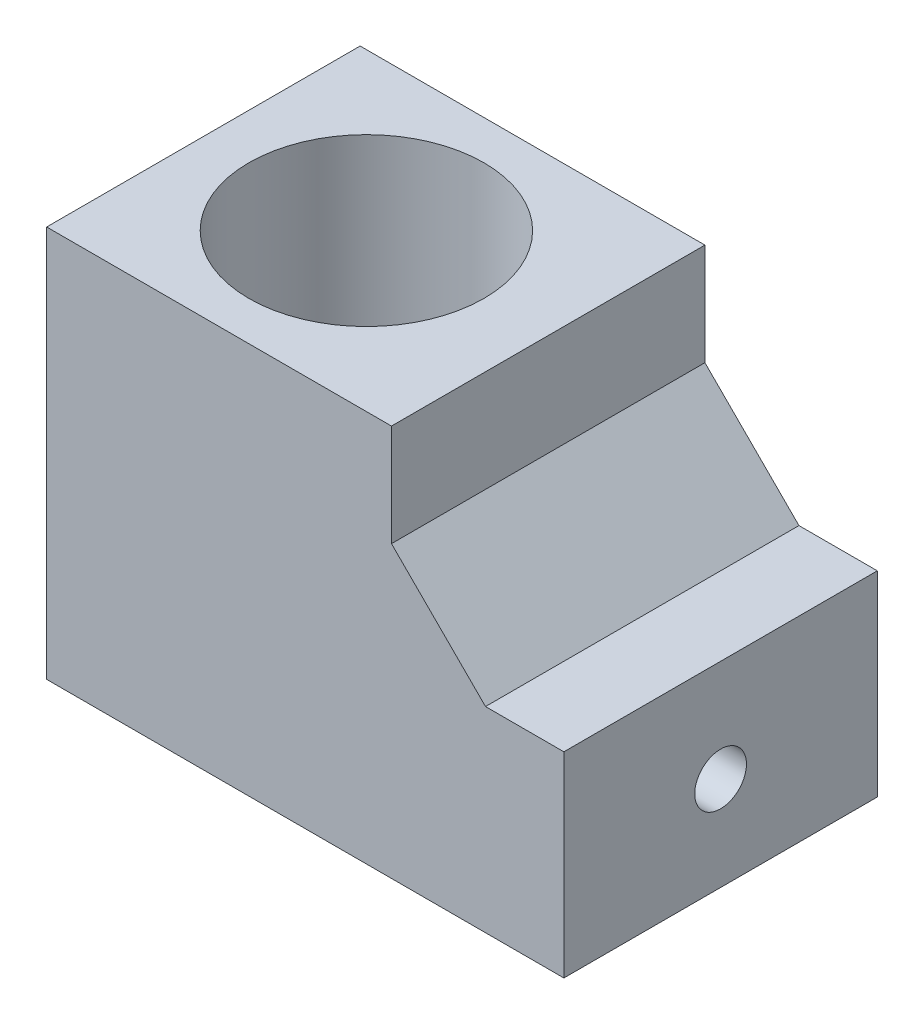
SolidWorks part; units mm, degrees
material "6061-T4 (SS)"
ref_plane "Piano frontale" through (0, 0, 0) normal (0, 0, 1) x (1, 0, 0)
ref_plane "Piano superiore" through (0, 0, 0) normal (0, 1, 0) x (1, 0, 0)
ref_plane "Piano destro" through (0, 0, 0) normal (1, 0, 0) x (0, 0, -1)
sketch "Schizzo1" plane through (0, 0, 0) normal (0, 0, 1) x (1, 0, 0)
  line L0 (0, 0) -> (33, 0)
  line L1 (33, 0) -> (33, 12.5)
  line L2 (33, 12.5) -> (28, 12.5)
  line L3 (28, 12.5) -> (22, 18.5)
  line L4 (22, 18.5) -> (22, 25)
  line L5 (22, 25) -> (0, 25)
  line L6 (0, 25) -> (0, 0)
  dimension "D1" = 33
  dimension "D2" = 22
  dimension "D3" = 25
  dimension "D4" = 12.5
  dimension "D5" = 45
  dimension "D6" = 5
extrude "Estrusione-Estrusione1" add sketch "Schizzo1" against normal blind 20
sketch "Schizzo2" plane through (0, 0, 0) normal (0, -1, 0) x (1, 0, 0)
  line L0 (0, -10) -> (33, -10) construction
  line L1 (0, -20) -> (0, 0) construction
  line L2 (33, -20) -> (33, 0) construction
  circle A0 centre (10.4, -10) radius 7.5
  dimension "D2" = 15
  dimension "D1" = 22.6
extrude "Taglio-Estrusione1" cut sketch "Schizzo2" against normal through all
sketch "Schizzo3" plane through (33, 0, 0) normal (1, 0, 0) x (0, 0, -1)
  line L0 (10, 0) -> (10, 12.5) construction
  line L1 (20, 0) -> (0, 0) construction
  line L2 (20, 12.5) -> (0, 12.5) construction
  point P6 (10, 6)
  dimension "D1" = 6
hole_wizard "Foro filettato M4-1" positions "Schizzo5" profile "Schizzo4" tap size "M4" standard "ISO"
sketch "Schizzo5" plane through (33, 0, 0) normal (1, 0, 0) x (0, 0, -1)
  point P0 (10, 6)
sketch "Schizzo4" plane through (33, 6, -10) normal (0, 1, 0) x (0, 0, -1)
  line L0 (0, 0) -> (0, 11.0914)
  line L1 (0, 11.0914) -> (1.65, 10.1)
  line L2 (1.65, 10.1) -> (1.65, 0)
  line L5 (1.65, 0) -> (0, 0)
  line L10 (0, 11.0914) -> (-1.65, 10.1) construction
  line L11 (0, -6.35) -> (0, 107.95) construction
  dimension "Tap Drill Dia." = 3.3
  dimension "Tap Drill Depth" = 10.1
  dimension "Drill Angle" = 118
cosmetic thread "Filettatura del foro1" parameters "D1"=8, "D2"=4
ref_axis "Assi1" through (10.4, 25, -10) along (0, -1, 0)
